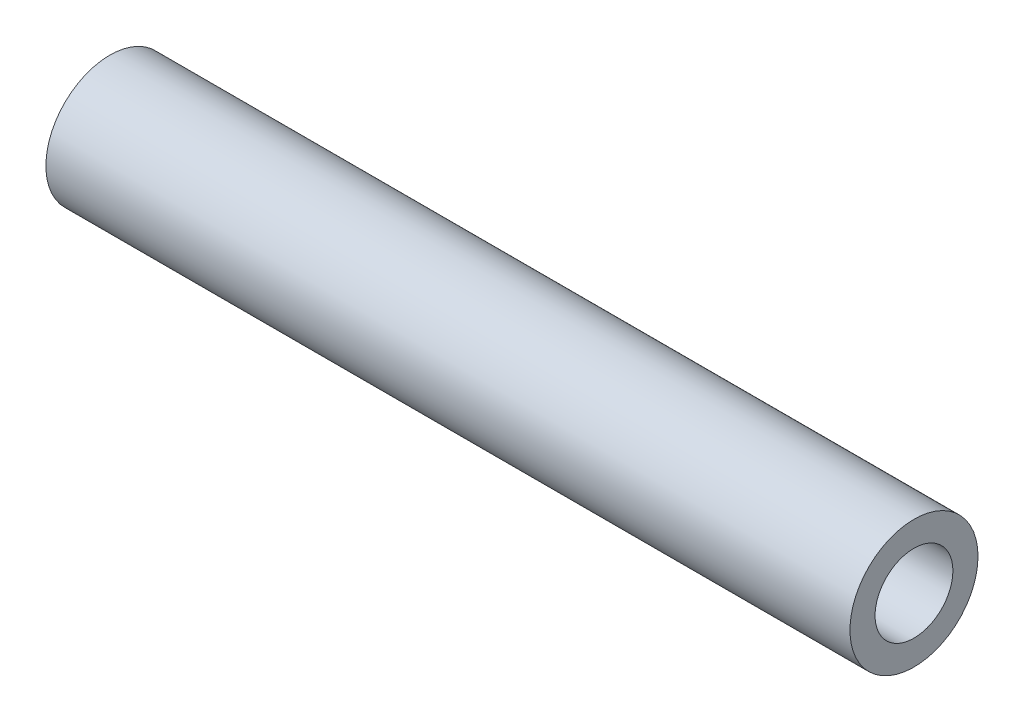
SolidWorks part; units mm, degrees
material "6061-T6 (SS)"
ref_plane "Front" through (0, 0, 0) normal (0, 0, 1) x (1, 0, 0)
ref_plane "Top" through (0, 0, 0) normal (0, 1, 0) x (1, 0, 0)
ref_plane "Right" through (0, 0, 0) normal (1, 0, 0) x (0, 0, -1)
sketch "Sketch1" plane through (0, 0, 0) normal (1, 0, 0) x (0, 0, -1)
  circle A0 centre (0, 0) radius 1.9304
  circle A1 centre (0, 0) radius 3.175
  dimension "D1" = 1.2446
  dimension "D2" = 6.35
extrude "Boss-Extrude1" add sketch "Sketch1" along normal mid plane 39.878
